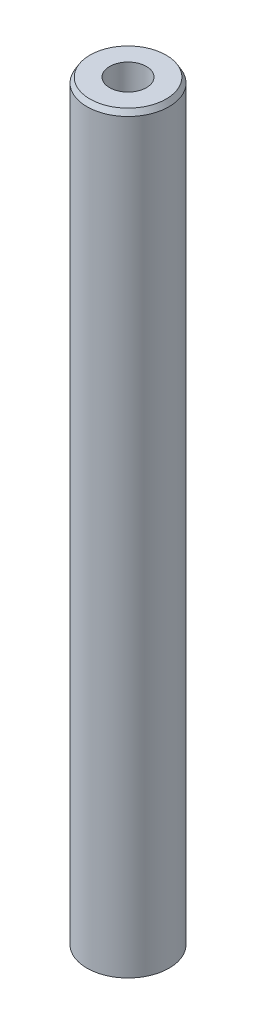
SolidWorks part; units mm, degrees
ref_plane "Front Plane" through (0, 0, 0) normal (0, 0, 1) x (1, 0, 0)
ref_plane "Top Plane" through (0, 0, 0) normal (0, 1, 0) x (1, 0, 0)
ref_plane "Right Plane" through (0, 0, 0) normal (1, 0, 0) x (0, 0, -1)
sketch "Sketch1" plane through (0, 0, 0) normal (0, 1, 0) x (1, 0, 0)
  circle A0 centre (0, 0) radius 22.5
  dimension "SHAFT_OD" = 45
extrude "Boss-Extrude1" add sketch "Sketch1" along normal blind 413.2559
sketch "Sketch2" plane through (0, 0, 0) normal (0, 1, 0) x (1, 0, 0)
  circle A0 centre (0, 0) radius 10.0917
  dimension "BORE_D" = 20.1834
extrude "Cut-Extrude1" cut sketch "Sketch2" along normal through all
chamfer "Chamfer1" distance 2.8185 angle 30 2 edges at (0, 413.2559, 22.5) (0, 0, 22.5) first distance on face at (0, 413.2559, 22.5) first distance on face at (0, 0, 10.0917)
